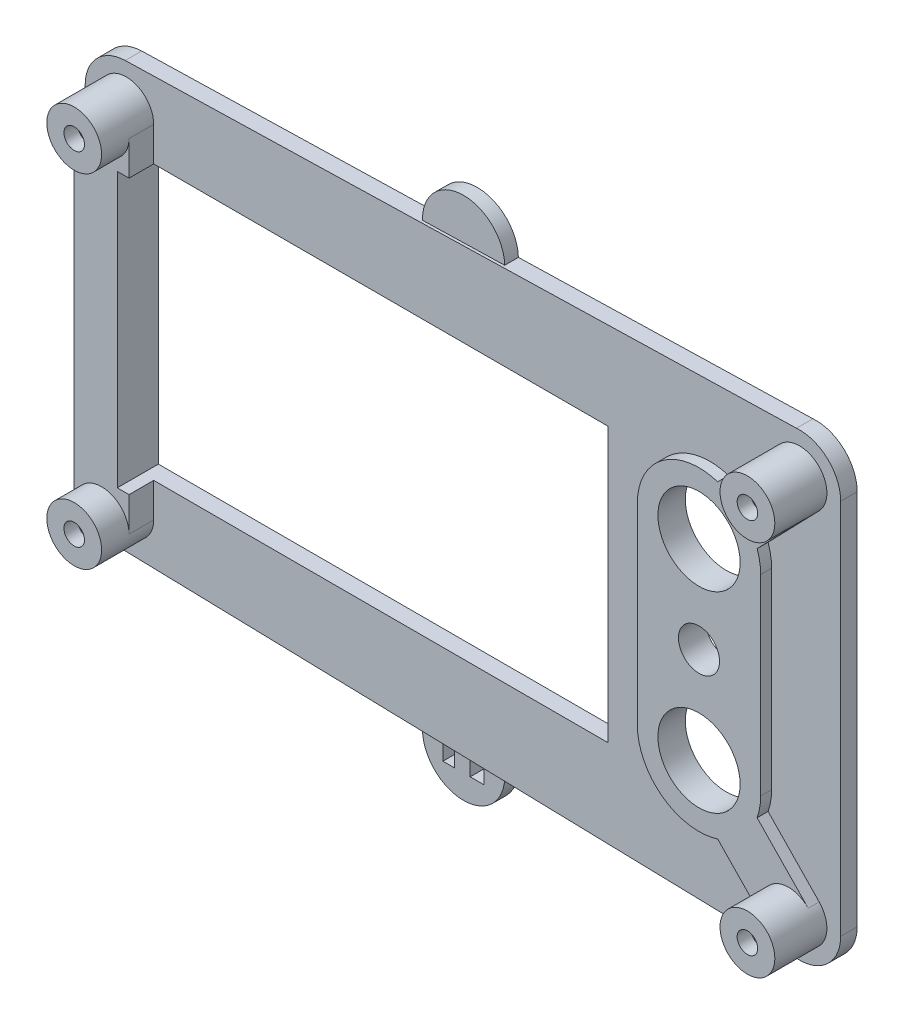
SolidWorks part; units mm, degrees
ref_plane "前视基准面" through (0, 0, 0) normal (0, 0, 1) x (1, 0, 0)
ref_plane "上视基准面" through (0, 0, 0) normal (0, 1, 0) x (1, 0, 0)
ref_plane "右视基准面" through (0, 0, 0) normal (1, 0, 0) x (0, 0, -1)
sketch "草图2" plane through (0, 0, 0) normal (0, 0, 1) x (1, 0, 0)
  line L4 (-49.1276, -26.25) -> (-49.1276, -1.25) construction
  line L7 (-51.1276, -26.25) -> (-51.1276, -1.25)
  line L10 (-47.1276, -26.25) -> (-47.1276, -1.25)
  line L13 (0, -27.5) -> (-6.533, -20.75) construction
  line L16 (-1.4371, -28.8909) -> (-7.9701, -22.1409)
  line L17 (-49.2041, 1.749) -> (-0.2201, 2.999)
  line L19 (1.4371, -26.1091) -> (-5.0959, -19.3591)
  line L21 (-49.2041, -29.249) -> (-0.2201, -30.499)
  line L22 (-6.533, -6.75) -> (0, 0) construction
  line L24 (-52.1276, -1.25) -> (-52.1276, -26.25)
  line L25 (-7.9701, -5.3591) -> (-1.4371, 1.3909)
  line L26 (3.0071, 0) -> (3.0071, -27.5)
  line L28 (-5.0959, -8.1409) -> (1.4371, -1.3909)
  line L41 (-47.9841, -13.75) -> (-47.9841, -3.75)
  line L42 (-13.9841, -13.75) -> (-13.9841, -3.75)
  line L43 (-47.9841, -3.75) -> (-13.9841, -3.75)
  line L45 (-13.9841, -13.75) -> (-13.9841, -23.75)
  line L46 (-47.9841, -13.75) -> (-47.9841, -23.75)
  line L47 (-13.9841, -23.75) -> (-47.9841, -23.75)
  line L48 (-6.533, -6.75) -> (-6.533, -20.75) construction
  line L49 (-2.033, -6.75) -> (-2.033, -20.75)
  line L50 (-11.033, -6.75) -> (-11.033, -20.75)
  circle A0 centre (0, 0) radius 0.75
  circle A1 centre (0, 0) radius 1.5
  circle A2 centre (0, -27.5) radius 0.75
  circle A3 centre (0, -27.5) radius 2
  circle A4 centre (-49.1276, -26.25) radius 0.75
  circle A5 centre (-49.1276, -26.25) radius 2
  circle A6 centre (-49.1276, -1.25) radius 0.75
  circle A7 centre (-49.1276, -1.25) radius 2
  circle A26 centre (-6.533, -13.75) radius 1.5
  circle A28 centre (-6.533, -6.75) radius 3
  circle A29 centre (-6.533, -20.75) radius 3
  arc A30 (-2.033, -6.75) -> (-11.033, -6.75) centre (-6.533, -6.75) ccw
  arc A31 (-11.033, -20.75) -> (-2.033, -20.75) centre (-6.533, -20.75) ccw
  arc A33 (3.0071, 0) -> (-0.2201, 2.999) centre (0, 0) ccw
  circle A34 centre (-49.1276, -1.25) radius 1.5
  arc A35 (-0.2201, -30.499) -> (3.0071, -27.5) centre (0, -27.5) ccw
  arc A36 (-49.2041, 1.749) -> (-52.1276, -1.25) centre (-49.1276, -1.25) ccw
  arc A37 (-52.1276, -26.25) -> (-49.2041, -29.249) centre (-49.1276, -26.25) ccw
  circle A38 centre (-49.1276, -26.25) radius 1.5
  circle A39 centre (0, -27.5) radius 1.5
  circle A40 centre (0, 0) radius 1.5
  circle A41 centre (0, 0) radius 2
  arc A42 (-51.1276, -26.25) -> (-47.1276, -26.25) centre (-49.1276, -26.25) ccw
  arc A43 (-47.1276, -1.25) -> (-51.1276, -1.25) centre (-49.1276, -1.25) ccw
  arc A44 (-1.4371, -28.8909) -> (1.4371, -26.1091) centre (0, -27.5) ccw
  arc A45 (-5.0959, -19.3591) -> (-7.9701, -22.1409) centre (-6.533, -20.75) ccw
  arc A46 (-7.9701, -5.3591) -> (-5.0959, -8.1409) centre (-6.533, -6.75) ccw
  arc A47 (1.4371, -1.3909) -> (-1.4371, 1.3909) centre (0, 0) ccw
  point P12 (-24.492, -0.625)
  point P18 (-49.1276, -13.75)
  point P19 (-48.9841, -13.75)
  point P24 (-24.492, -26.875)
  point P26 (-3.2665, -24.125)
  point P29 (0, -13.75)
  point P33 (-3.2665, -3.375)
  point P39 (-24.492, -0.625)
  point P46 (-24.492, -26.875)
  point P51 (-48.9841, -13.75)
  point P58 (0, -13.75)
  point P75 (-6.533, -13.75)
  dimension "D2" = 1.5
  dimension "D3" = 4
  dimension "D7" = 10
  dimension "D10" = 6
  dimension "D11" = 3
  dimension "D5" = 27.5
  dimension "D8" = 10
  dimension "D9" = 7
  dimension "D12" = 34
extrude "凸台-拉伸1" add sketch "草图2" along normal blind 1.2 contours L24 A37 L21 A35 L26 A33 L17 A36 L45 L47 L46 L41 L43 L42 A1 A3 A5 A7 A31 L50 A30 L49 region at (-24.6956, 1.729, 0)
extrude "凸台-拉伸7" add sketch "草图2<8>" along normal blind 2 contours L50 A31 L49 A30 A28 A26 A29 region at (-9.0426, -24.1837, 0)
sketch "草图2<8>" plane through (0, 0, 0) normal (0, 0, 1) x (1, 0, 0) same geometry as "草图2"
extrude "凸台-拉伸8" add sketch "草图2<9>" along normal blind 5 contours A7 A34 region at (-49.1276, 0.6934, 0)
sketch "草图2<9>" plane through (0, 0, 0) normal (0, 0, 1) x (1, 0, 0) same geometry as "草图2"
extrude "凸台-拉伸9" add sketch "草图2<10>" along normal blind 5 contours A3 A39 region at (-1.3516, -26.1035, 0)
sketch "草图2<10>" plane through (0, 0, 0) normal (0, 0, 1) x (1, 0, 0) same geometry as "草图2"
extrude "凸台-拉伸10" add sketch "草图2<11>" along normal blind 5 contours A41 A1 region at (0.729, 1.8015, 0)
sketch "草图2<11>" plane through (0, 0, 0) normal (0, 0, 1) x (1, 0, 0) same geometry as "草图2"
extrude "凸台-拉伸11" add sketch "草图2<12>" along normal blind 5 contours A5 A38 region at (-49.1276, -24.3066, 0)
sketch "草图2<12>" plane through (0, 0, 0) normal (0, 0, 1) x (1, 0, 0) same geometry as "草图2"
extrude "凸台-拉伸12" add sketch "草图2<13>" along normal blind 5 contours A34 A6 region at (-50.5852, -1.25, 0)
sketch "草图2<13>" plane through (0, 0, 0) normal (0, 0, 1) x (1, 0, 0) same geometry as "草图2"
extrude "凸台-拉伸13" add sketch "草图2<14>" along normal blind 5 contours A38 A4 region at (-50.5852, -26.25, 0)
sketch "草图2<14>" plane through (0, 0, 0) normal (0, 0, 1) x (1, 0, 0) same geometry as "草图2"
extrude "凸台-拉伸14" add sketch "草图2<15>" along normal blind 5 contours A1 A0 region at (-1.4576, 0, 0)
sketch "草图2<15>" plane through (0, 0, 0) normal (0, 0, 1) x (1, 0, 0) same geometry as "草图2"
extrude "凸台-拉伸15" add sketch "草图2<16>" along normal blind 5 contours A39 A2 region at (-1.4576, -27.5, 0)
sketch "草图2<16>" plane through (0, 0, 0) normal (0, 0, 1) x (1, 0, 0) same geometry as "草图2"
extrude "切除-拉伸4" cut sketch "草图2<19>" along normal blind 4 contours A34 A6 region at (-50.5852, -1.25, 0)
sketch "草图2<19>" plane through (0, 0, 0) normal (0, 0, 1) x (1, 0, 0) same geometry as "草图2"
extrude "切除-拉伸5" cut sketch "草图2<20>" along normal blind 4 contours A38 A4 region at (-50.5852, -26.25, 0)
sketch "草图2<20>" plane through (0, 0, 0) normal (0, 0, 1) x (1, 0, 0) same geometry as "草图2"
extrude "切除-拉伸6" cut sketch "草图2<21>" along normal blind 4 contours A39 A2 region at (-1.4576, -27.5, 0)
sketch "草图2<21>" plane through (0, 0, 0) normal (0, 0, 1) x (1, 0, 0) same geometry as "草图2"
extrude "切除-拉伸7" cut sketch "草图2<22>" along normal blind 4 contours A1 A0 region at (-1.4576, 0, 0)
sketch "草图2<22>" plane through (0, 0, 0) normal (0, 0, 1) x (1, 0, 0) same geometry as "草图2"
extrude "凸台-拉伸16" add sketch "草图2<23>" along normal blind 3 contours A7 L7 A5 L10 L47 L46 L41 L43 region at (-49.5105, -13.75, 0)
sketch "草图2<23>" plane through (0, 0, 0) normal (0, 0, 1) x (1, 0, 0) same geometry as "草图2"
extrude "凸台-拉伸18" add sketch "草图2<24>" along normal blind 2 contours A31 L16 A3 L19 | L16 A31 L19 A29 | L28 A30 L25 A28 | A41 L25 A30 L28 region at (-2.2831, -25.1411, 0) region at (-4.0683, -23.2966, 0) region at (-4.0683, -4.2034, 0) region at (-2.2831, -2.3589, 0)
sketch "草图2<24>" plane through (0, 0, 0) normal (0, 0, 1) x (1, 0, 0) same geometry as "草图2"
sketch "草图4" plane through (0, 0, 0) normal (0, 0, -1) x (-1, 0, 0)
  line L0 (24.7121, 2.374) -> (24.7121, -0.626) construction
  line L1 (49.2041, 1.749) -> (0.2201, 2.999) construction
  line L2 (27.7121, 2.374) -> (27.7121, -0.626)
  line L3 (21.7121, 2.374) -> (21.7121, -0.626)
  line L4 (24.7121, -29.874) -> (24.7121, -26.874) construction
  line L5 (49.2041, -29.249) -> (0.2201, -30.499) construction
  line L6 (21.7121, -29.874) -> (21.7121, -26.874)
  line L7 (27.7121, -29.874) -> (27.7121, -26.874)
  arc A0 (27.7121, 2.374) -> (21.7121, 2.374) centre (24.7121, 2.374) ccw
  arc A1 (21.7121, -0.626) -> (27.7121, -0.626) centre (24.7121, -0.626) ccw
  arc A2 (21.7121, -29.874) -> (27.7121, -29.874) centre (24.7121, -29.874) ccw
  arc A3 (27.7121, -26.874) -> (21.7121, -26.874) centre (24.7121, -26.874) ccw
  point P4 (24.7121, 0.874)
  point P9 (24.7121, -28.374)
extrude "凸台-拉伸19" add sketch "草图4" against normal blind 1 contours L3 A1 L2 A0 | L7 A3 L6 A2
sketch "草图5" plane through (0, 0, 1) normal (0, 0, 1) x (1, 0, 0)
  line L0 (-25.3687, -28.5474) -> (-25.3687, -31.1454)
  line L1 (-25.3687, -28.5474) -> (-26.2229, -28.5474)
  line L2 (-25.3687, -31.1454) -> (-26.2229, -31.1454)
  line L3 (-26.2229, -28.5474) -> (-26.2229, -31.1454)
  line L4 (-25.3687, -28.5474) -> (-26.2229, -31.1454) construction
  line L5 (-25.3687, -31.1454) -> (-26.2229, -28.5474) construction
  line L6 (-23.2241, -28.6615) -> (-23.2241, -31.1368)
  line L7 (-23.2241, -28.6615) -> (-24.2295, -28.6615)
  line L8 (-23.2241, -31.1368) -> (-24.2295, -31.1368)
  line L9 (-24.2295, -28.6615) -> (-24.2295, -31.1368)
  line L10 (-23.2241, -28.6615) -> (-24.2295, -31.1368) construction
  line L11 (-23.2241, -31.1368) -> (-24.2295, -28.6615) construction
  line L12 (-21.7131, -29.9506) -> (-27.7121, -29.7975) construction
  point P0 (-25.7958, -29.8464)
  point P1 (-25.7958, -29.8464)
  point P2 (-23.7268, -29.8992)
extrude "切除-拉伸9" cut sketch "草图5" against normal blind 1 contours L0 L1 L3 L2 | L6 L7 L9 L8
